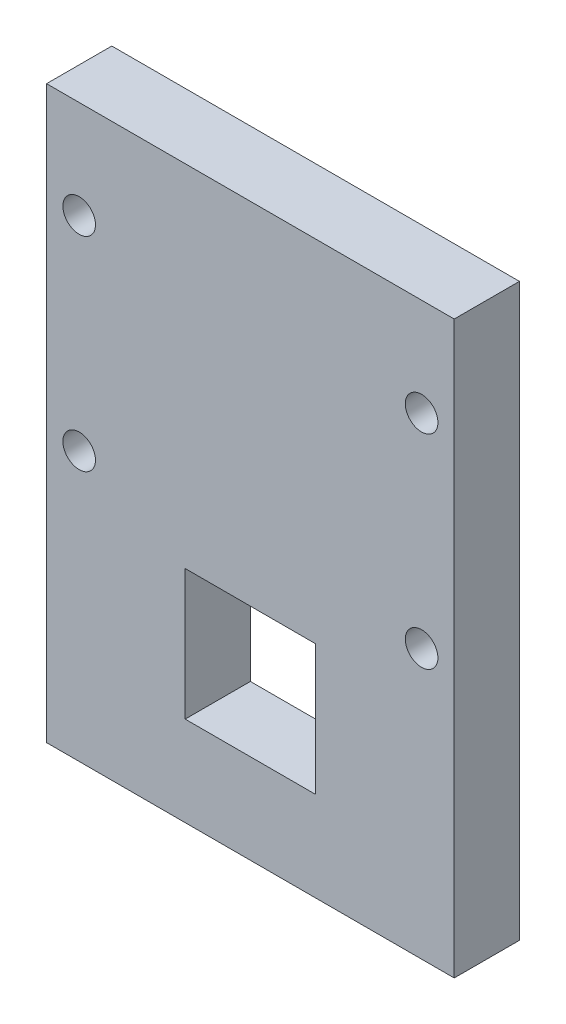
SolidWorks part; units mm, degrees
ref_plane "Front" through (0, 0, 0) normal (0, 0, 1) x (1, 0, 0)
ref_plane "Top" through (0, 0, 0) normal (0, 1, 0) x (1, 0, 0)
ref_plane "Right" through (0, 0, 0) normal (1, 0, 0) x (0, 0, -1)
sketch "Sketch1" plane through (0, 0, 0) normal (0, 0, 1) x (1, 0, 0)
  line L0 (-23, 16.5) -> (-2, 16.5) construction
  line L1 (0, 0) -> (-25, 0)
  line L2 (0, 0) -> (0, 35)
  line L3 (0, 35) -> (-25, 35)
  line L4 (-25, 0) -> (-25, 35)
  line L5 (-16.5, 13.5) -> (-8.5, 13.5)
  line L6 (-16.5, 13.5) -> (-16.5, 5.5)
  line L7 (-16.5, 5.5) -> (-8.5, 5.5)
  line L8 (-8.5, 13.5) -> (-8.5, 5.5)
  line L9 (-23, 29) -> (-2, 29) construction
  circle A0 centre (-23, 29) radius 1
  circle A1 centre (-23, 16.5) radius 1
  circle A2 centre (-2, 16.5) radius 1
  circle A3 centre (-2, 29) radius 1
  point P17 (0, 0)
  point P18 (0, 0)
  point P19 (0, 0)
  dimension "D2" = 2
  dimension "D1" = 8
  dimension "D3" = 21
  dimension "D4" = 25
  dimension "D5" = 8.5
  dimension "D6" = 35
  dimension "D7" = 5.5
  dimension "D8" = 12.5
  dimension "D9" = 6
  dimension "D10" = 2
extrude "Boss-Extrude1" add sketch "Sketch1" along normal blind 4 contours L8 L5 L6 L7 | L3 L4 L1 L2 | A1 | A0 | A3 | A2 region at (-12.5, 9.5, 0)
